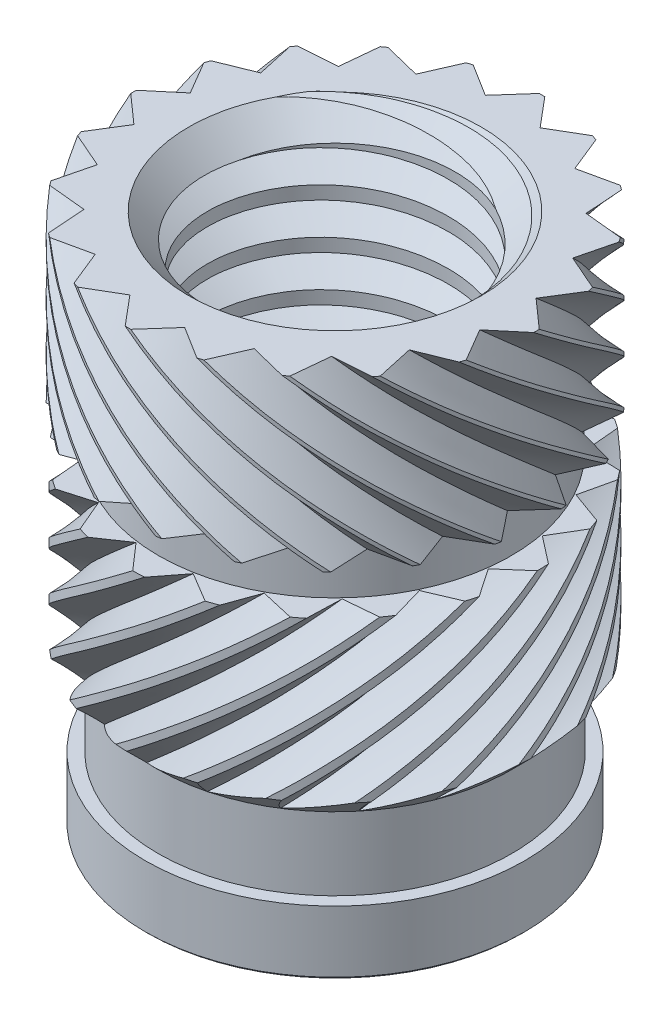
SolidWorks part; units mm, degrees
ref_plane "Front Plane" through (0, 0, 0) normal (0, 0, 1) x (1, 0, 0)
ref_plane "Top Plane" through (0, 0, 0) normal (0, 1, 0) x (1, 0, 0)
ref_plane "Right Plane" through (0, 0, 0) normal (1, 0, 0) x (0, 0, -1)
sketch "Sketch1" plane through (0, 0, 0) normal (0, 0, 1) x (1, 0, 0)
  line L0 (3.15, 0) -> (1.8553, 0)
  line L1 (3.15, 0) -> (3.15, -2.5895)
  line L2 (3.15, -2.5895) -> (2.719, -2.5895)
  line L3 (0, 2.5961) -> (0, -10.0589) construction
  line L4 (3.119, -3.2395) -> (3.119, -5.6995)
  line L5 (3.119, -3.2395) -> (2.719, -3.2395)
  line L6 (2.729, -6.0895) -> (2.729, -7.2116)
  line L7 (2.9232, -8.1616) -> (2.8848, -8.2)
  line L8 (2.729, -7.2116) -> (2.9232, -7.2116)
  line L9 (2.719, -2.5895) -> (2.719, -3.2395)
  line L10 (2.9232, -7.2116) -> (2.9232, -8.1616)
  line L11 (1.8553, 0) -> (1.8553, -8.2)
  line L12 (1.8553, -8.2) -> (2.8848, -8.2)
  line L13 (2.729, -6.0895) -> (3.119, -5.6995)
  dimension "D3" = 2.5895
  dimension "D4" = 0.65
  dimension "D5" = 0.431
  dimension "D6" = 0.4
  dimension "D7" = 0.39
  dimension "D8" = 0.39
  dimension "D9" = 2.46
  dimension "D10" = 1.1221
  dimension "D11" = 0.95
  dimension "D12" = 0.1942
revolve "Revolve1" add sketch "Sketch1" angle 360 about L3
sketch "Sketch2" plane through (0, 0, 0) normal (0, 1, 0) x (1, 0, 0)
  circle A0 centre (0, 0) radius 1.8553
curve "Helix/Spiral1" pitch 0.7 height 9.1 radius 1.8553 centre (0, 0, 0) axis (0, -1, 0) start towards (0, 0, 1)
sketch "Sketch3" plane through (0, 0, 0) normal (1, 0, 0) x (0, 0, -1)
  line L0 (-1.8553, 0) -> (-2.2847, 0.2479)
  line L2 (-1.8553, 0.4958) -> (-1.8553, 0)
  line L3 (-1.8553, 0.4958) -> (-2.2847, 0.2479)
chamfer "Chamfer2" distance 0.4 angle 45 1 edges at (0, 0, 1.8553)
sweep "Cut-Sweep2" cut profiles "Sketch3" path "Helix/Spiral1" align with end faces yes
sketch "Sketch4" plane through (0, 0, 0) normal (0, 1, 0) x (1, 0, 0)
  circle A0 centre (0, 0) radius 3.15
curve "Helix/Spiral2" pitch 15 height 2.7 radius 3.15 left hand yes centre (0, 0, 0) axis (0, -1, 0) start towards (0, 0, 1)
sketch "Sketch5" plane through (0, 0, 0) normal (0, 1, 0) x (1, 0, 0)
  line L1 (0, -3.15) -> (0.3911, -2.7096)
  line L3 (0.3911, -2.7096) -> (0.8908, -3.0214)
  arc A0 (0, -3.15) -> (0.8908, -3.0214) centre (0.3911, -2.7096) ccw
  circle A2 centre (0, 0) radius 3.15 construction
sweep "Cut-Sweep7" cut profiles "Sketch5" path "Helix/Spiral2" align with end faces yes
sketch "Sketch6" plane through (0, 0, 0) normal (0, 0, 1) x (1, 0, 0)
  line L0 (0, 1.831) -> (0, -10.0346) construction
pattern_circular "CirPattern1" count 20 over 360 about axis through (0, 1.831, 0) along (0, -1, 0) of "Cut-Sweep7"
sketch "Sketch7" plane through (0, -3.2395, 0) normal (0, 1, 0) x (1, 0, 0)
  circle A1 centre (0, 0) radius 3.119
curve "Helix/Spiral3" pitch 15 height 2.925 radius 3.119 centre (0, -3.2395, 0) axis (0, -1, 0) start towards (0, 0, 1)
sketch "Sketch8" plane through (0, -3.2395, 0) normal (0, 1, 0) x (1, 0, 0)
  line L3 (-0.3513, -2.7164) -> (0, -3.119)
  line L4 (-0.3513, -2.7164) -> (-0.7935, -3.0164)
  circle A0 centre (0, 0) radius 3.119 construction
  arc A1 (0, -3.119) -> (-0.7935, -3.0164) centre (-0.4001, -3.0932) cw
sweep "Cut-Sweep9" cut profiles "Sketch8" path "Helix/Spiral3" align with end faces yes
pattern_circular "CirPattern4" count 20 over 360 about axis through (0, 1.831, 0) along (0, -1, 0) of "Cut-Sweep9"
